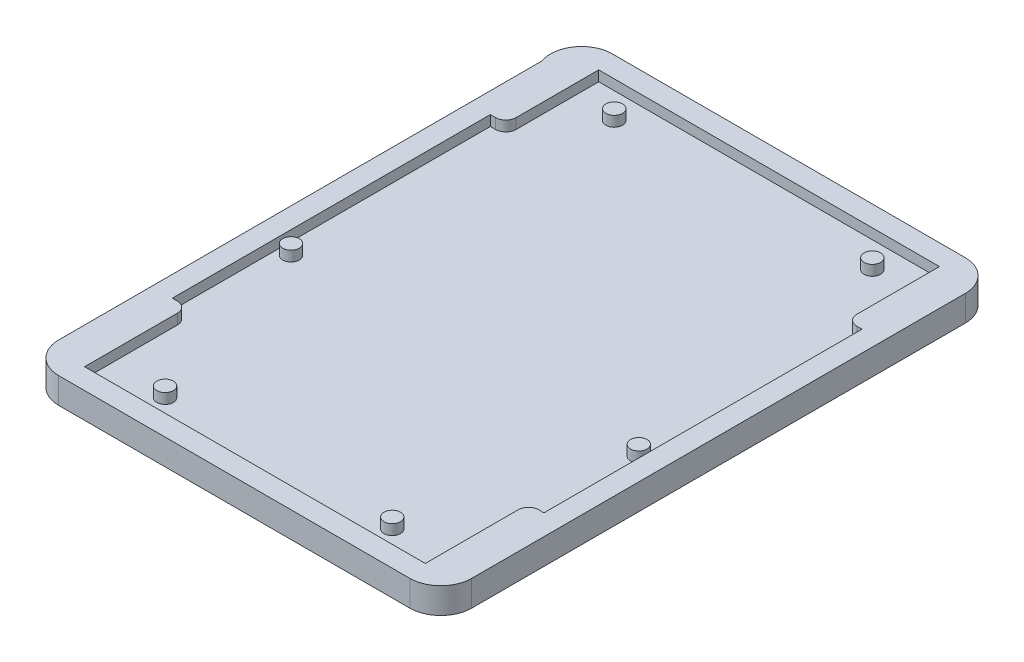
SolidWorks part; units mm, degrees
material "锌 AC41A 合金，作为铸件"
ref_plane "前视基准面" through (0, 0, 0) normal (0, 0, 1) x (1, 0, 0)
ref_plane "上视基准面" through (0, 0, 0) normal (0, 1, 0) x (1, 0, 0)
ref_plane "右视基准面" through (0, 0, 0) normal (1, 0, 0) x (0, 0, -1)
sketch "草图1" plane through (0, 0, 0) normal (0, 1, 0) x (1, 0, 0)
  line L0 (0.75, -5) -> (11, -5) construction
  line L1 (0, 0) -> (72, 0)
  line L2 (0, 0) -> (0, -99.6)
  line L3 (0, -99.6) -> (72, -99.6)
  line L4 (72, 0) -> (72, -99.6)
  line L5 (0.75, -5) -> (0.75, -15) construction
  line L6 (3.75, -95) -> (14, -95) construction
  line L7 (3.75, -95) -> (3.75, -85) construction
  line L8 (36, -99.6) -> (36, -33.3414) construction
  line L9 (68.25, -95) -> (68.25, -85) construction
  line L10 (68.25, -95) -> (58, -95) construction
  line L11 (71.25, -5) -> (71.25, -15) construction
  line L12 (71.25, -5) -> (61, -5) construction
  line L13 (14, -95) -> (14, -58.92) construction
  line L14 (14, -58.92) -> (2.31, -58.92) construction
  circle A1 centre (11, -5) radius 1.6
  circle A5 centre (14, -95) radius 1.6
  circle A6 centre (58, -95) radius 1.6
  circle A10 centre (61, -5) radius 1.6
  circle A12 centre (2.31, -58.92) radius 1.6
  circle A13 centre (69.69, -58.92) radius 1.6
  dimension "D8" = 3.2
  dimension "D14" = 3.2
  dimension "D17" = 3.2
  dimension "D5" = 50
  dimension "D16" = 44
  dimension "D1" = 72
  dimension "D2" = 99.6
  dimension "D6" = 10
  dimension "D15" = 10
extrude "凸台-拉伸1" add sketch "草图1" along normal blind 2
fillet "圆角1" radius 3 4 edges at (0, 1, 0) (72, 1, 0) (72, 1, 99.6) (0, 1, 99.6)
sketch "草图7" plane through (0, 2, 0) normal (0, 1, 0) x (1, 0, 0)
  line L0 (3, -99.6) -> (69, -99.6) construction
  line L1 (34.9132, -101.7843) -> (37.0868, -101.7843)
  line L2 (34.9132, -101.7843) -> (34.9132, -97.4157)
  line L3 (34.9132, -97.4157) -> (37.0868, -97.4157)
  line L4 (37.0868, -101.7843) -> (37.0868, -97.4157)
  line L5 (34.9132, -101.7843) -> (37.0868, -97.4157) construction
  line L6 (34.9132, -97.4157) -> (37.0868, -101.7843) construction
  point P0 (36, -99.6)
extrude "切除-拉伸1" cut sketch "草图7" against normal blind 10
sketch "草图8" plane through (0, 2, 0) normal (0, 1, 0) x (1, 0, 0)
  line L0 (0, -96.6) -> (0, -99.6) construction
  line L1 (0, -99.6) -> (3, -99.6) construction
  line L2 (3, -99.6) -> (3, -79.6) construction
  line L3 (3, -79.6) -> (0, -79.6) construction
  line L4 (0, -3) -> (0, -96.6) construction
  line L5 (0, -79.6) -> (0, -96.6) construction
  line L6 (3, -79.6) -> (3, -99.6)
  line L7 (3, -79.6) -> (0, -79.6)
  line L8 (36, -97.4157) -> (36, -85.1744) construction
  line L9 (37.0868, -97.4157) -> (34.9132, -97.4157) construction
  line L10 (72, -79.6) -> (72, -96.6) construction
  line L11 (69, -79.6) -> (72, -79.6) construction
  line L12 (69, -99.6) -> (69, -79.6) construction
  line L13 (72, -99.6) -> (69, -99.6) construction
  line L14 (37.0868, -97.4157) -> (37.0868, -99.6)
  line L15 (37.0868, -99.6) -> (69, -99.6)
  line L16 (72, -96.6) -> (72, -3)
  line L17 (69, 0) -> (3, 0)
  line L18 (0, -3) -> (0, -96.6)
  line L19 (3, -99.6) -> (34.9132, -99.6)
  line L20 (34.9132, -99.6) -> (34.9132, -97.4157)
  line L21 (34.9132, -97.4157) -> (37.0868, -97.4157)
  line L26 (0, -79.6) -> (0, -96.6)
  line L30 (72, -96.6) -> (72, -99.6) construction
  line L31 (72, -79.6) -> (72, -96.6)
  line L32 (69, -79.6) -> (72, -79.6)
  line L33 (69, -79.6) -> (69, -99.6)
  line L34 (72, -96.6) -> (72, -3) construction
  line L36 (72, -96.6) -> (72, -79.6)
  line L37 (69, -18) -> (72, -18)
  line L38 (0, -3) -> (0, -18)
  line L39 (3, 0) -> (3, -18)
  line L40 (3, -18) -> (0, -18)
  line L41 (69, 0) -> (69, -18)
  line L42 (72, -3) -> (72, -18)
  line L44 (0, -79.6) -> (0, -96.6)
  arc A0 (72, -96.6) -> (69, -99.6) centre (69, -96.6) cw
  arc A2 (3, 0) -> (0, -3) centre (3, -3) ccw construction
  arc A4 (69, -99.6) -> (72, -96.6) centre (69, -96.6) ccw
  arc A5 (72, -3) -> (69, 0) centre (69, -3) ccw
  arc A6 (3, 0) -> (0, -3) centre (3, -3) ccw
  arc A7 (0, -96.6) -> (3, -99.6) centre (3, -96.6) ccw
  arc A11 (0, -96.6) -> (3, -99.6) centre (3, -96.6) ccw
  arc A12 (3, 0) -> (0, -3) centre (3, -3) ccw
  arc A14 (69, 0) -> (72, -3) centre (69, -3) cw
  line M20 (0, -3) -> (0, -96.6)
  arc M21 (0, -96.6) -> (3, -99.6) centre (3, -96.6) ccw
  dimension "D1" = 0
  dimension "D2" = 15
extrude "切除-拉伸2" cut sketch "草图8" against normal blind 10 contours L6 L7 M20 M21 | A0 L33 L32 L31 | A12 L38 L40 L39 region at (1.5276, 2, 89.2897)
fillet "圆角2" radius 2 2 edges at (3, 1, 79.6) (69, 1, 79.6)
ref_plane "基准面2" through (36, 0, 0) normal (1, 0, 0) x (0, 0, -1)
mirror "镜向2" about plane through (36, 0, 0) normal (1, 0, 0) of "切除-拉伸2"
sketch "草图9" plane through (0, 2, 0) normal (0, 1, 0) x (1, 0, 0)
  line L5 (34.9132, -97.4157) -> (37.0868, -97.4157)
  line L6 (34.9132, -97.4157) -> (34.9132, -99.6)
  line L7 (34.9132, -99.6) -> (37.0868, -99.6)
  line L8 (37.0868, -97.4157) -> (37.0868, -99.6)
extrude "凸台-拉伸5" add sketch "草图9" against normal blind 2
fillet "圆角4" radius 2 2 edges at (69, 1, 18) (3, 1, 18)
fillet "圆角5" radius 2 2 edges at (3, 1, 79.6) (69, 1, 79.6)
sketch "草图2" plane through (0, 2, 0) normal (0, 1, 0) x (1, 0, 0)
  line L0 (69, 0) -> (3, 0) construction
  circle A0 centre (36, 0) radius 0.8694
ref_plane "基准面1" through (0, -3, 0) normal (0, -1, 0) x (-1, 0, 0)
sketch "草图6" plane through (0, -3, 0) normal (0, -1, 0) x (-1, 0, 0)
  line L0 (-2, 4) -> (-70, 4)
  line L2 (-70, -103.6) -> (-2, -103.6)
  line L3 (4, -97.6) -> (4, -4)
  line L4 (-72, -18) -> (-74, -18) construction
  line L5 (-74, -18) -> (-76, -18) construction
  line L6 (-76, -18) -> (-76, -2)
  line L7 (-76, -18) -> (-76, -97.6)
  arc A2 (-2, -103.6) -> (4, -97.6) centre (-2, -97.6) ccw
  arc A3 (4, -4) -> (-2, 4) centre (-1.6533, -1.99) ccw
  arc A4 (-76, -97.6) -> (-70, -103.6) centre (-70, -97.6) ccw
  arc A5 (-76, -2) -> (-70, 4) centre (-70, -2) cw
  dimension "D1" = 6
  dimension "D4" = 6
  dimension "D5" = 6
  dimension "D2" = 2
  dimension "D3" = 2
extrude "凸台-拉伸4" add sketch "草图6" against normal blind 5 separate body
combine bodies "组合1" operation type subtract main body 110 bodies to subtract 116
